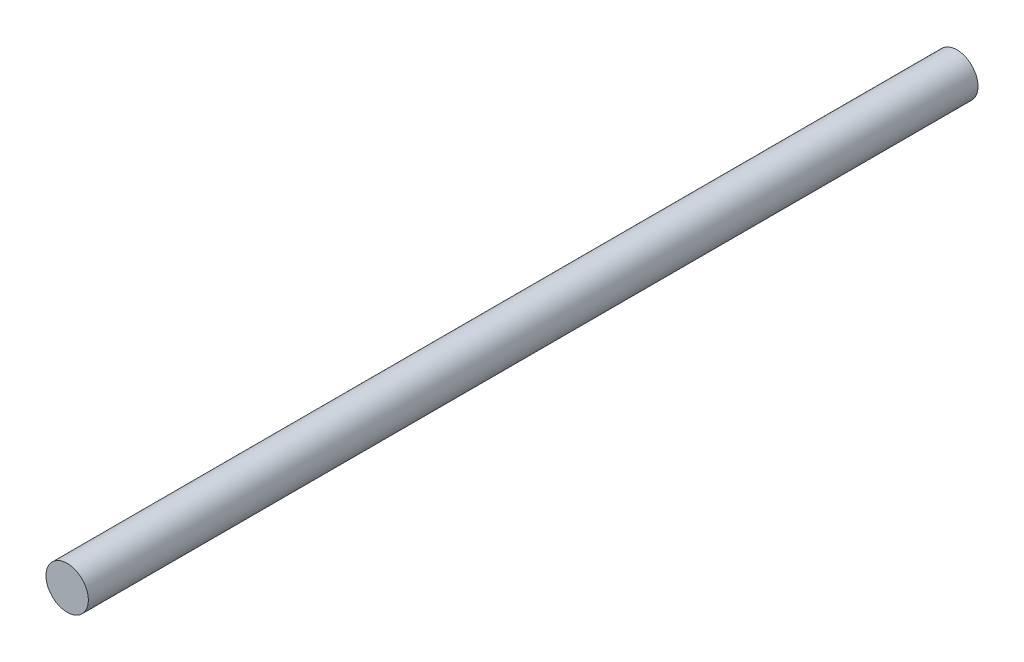
SolidWorks part; units mm, degrees
ref_plane "Спереди" through (0, 0, 0) normal (0, 0, 1) x (1, 0, 0)
ref_plane "Сверху" through (0, 0, 0) normal (0, 1, 0) x (1, 0, 0)
ref_plane "Справа" through (0, 0, 0) normal (1, 0, 0) x (0, 0, -1)
sketch "Эскиз1" plane through (0, 0, 0) normal (0, 0, 1) x (1, 0, 0)
  circle A0 centre (0, 0) radius 2
  dimension "D1" = 4
extrude "Шпилька на тяги" add sketch "Эскиз1" along normal blind 84
